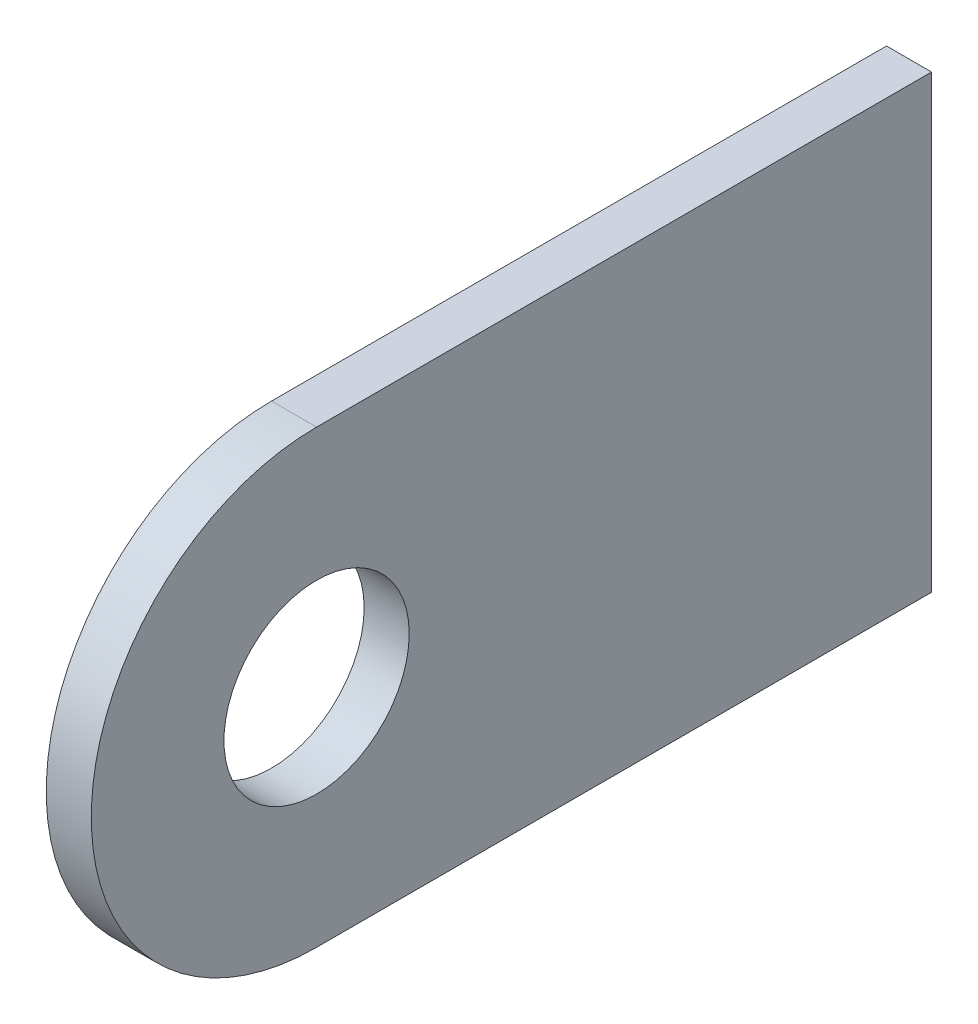
SolidWorks part; units mm, degrees
material "AISI 4130 Steel, annealed at 865C"
ref_plane "X-Y Datum" through (0, 0, 0) normal (0, 0, 1) x (1, 0, 0)
ref_plane "X-Z Datum" through (0, 0, 0) normal (0, 1, 0) x (1, 0, 0)
ref_plane "Y-Z Datum" through (0, 0, 0) normal (1, 0, 0) x (0, 0, -1)
sketch "Sketch1" plane through (0, 0, 0) normal (1, 0, 0) x (0, 0, -1)
  line L0 (3.175, -7.9375) -> (3.175, 7.9375)
  line L4 (-18.4937, -7.9375) -> (3.175, -7.9375)
  line L5 (-18.4937, 7.9375) -> (3.175, 7.9375)
  arc A1 (-18.4937, -7.9375) -> (-18.4937, 7.9375) centre (-18.4937, 0) cw
  point P4 (3.175, 0)
  dimension "D1" = 21.6687
  dimension "D2" = 7.9375
  dimension "D3" = 3.175
extrude "Boss-Extrude1" add sketch "Sketch1" along normal blind 1.5875
hole_wizard "1/4 Clearance Hole1" positions "Sketch2" profile "Sketch3" hole size "1/4" standard "ANSI Inch" end condition through all
sketch "Sketch2" plane through (1.5875, 0, 0) normal (1, 0, 0) x (0, 0, -1)
  point P0 (-18.4937, 0)
sketch "Sketch3" plane through (1.5875, 0, 18.4937) normal (0, 1, 0) x (0, 0, -1)
  line L0 (0, 0) -> (0, 1.5875)
  line L1 (0, 1.5875) -> (3.2639, 1.5875)
  line L2 (3.2639, 1.5875) -> (3.2639, 0)
  line L5 (3.2639, 0) -> (0, 0)
  line L11 (0, -6.35) -> (0, 107.95) construction
  dimension "Thru Hole Dia." = 6.5278
  dimension "Thru Hole Depth" = 1.5875
